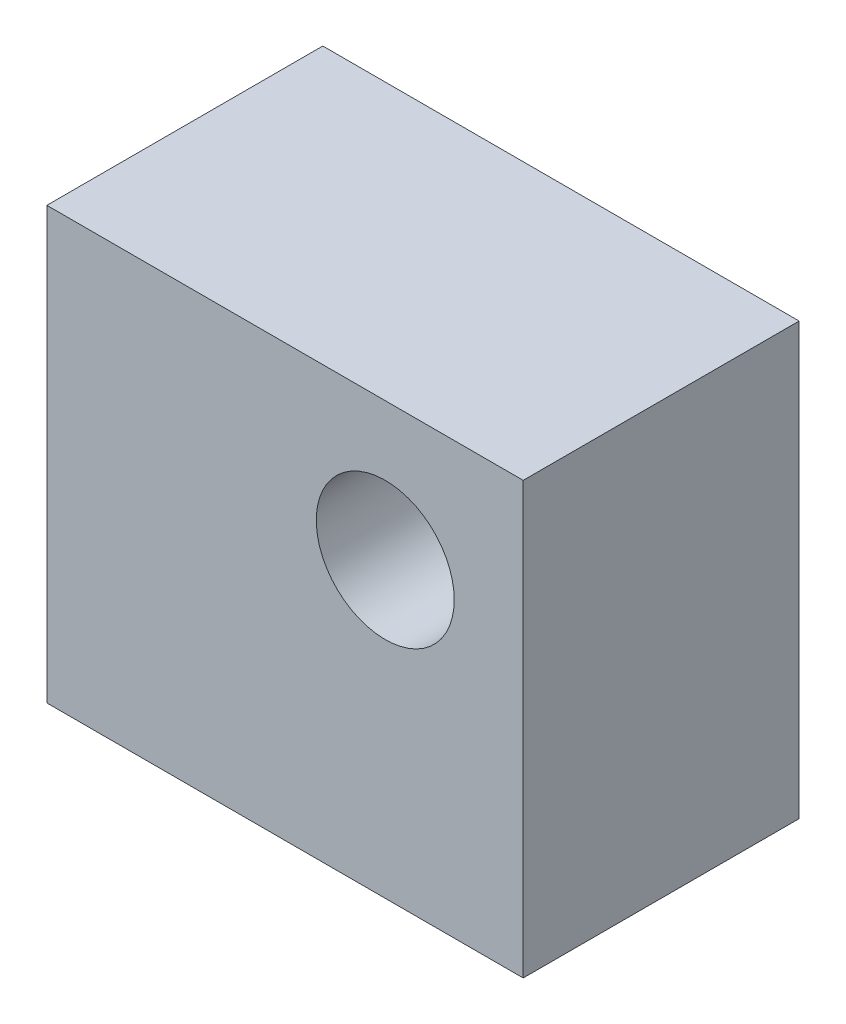
SolidWorks part; units mm, degrees
material "1060 Alloy"
ref_plane "Front" through (0, 0, 0) normal (0, 0, 1) x (1, 0, 0)
ref_plane "Top" through (0, 0, 0) normal (0, 1, 0) x (1, 0, 0)
ref_plane "Right" through (0, 0, 0) normal (1, 0, 0) x (0, 0, -1)
sketch "Sketch3" plane through (0, 0, 0) normal (0, 0, 1) x (1, 0, 0)
  line L0 (-0.127, -6.35) -> (30.1755, -6.35)
  line L1 (0, 0) -> (21.9242, 0)
  line L2 (0, 0) -> (0, -19.8376)
  line L3 (0, -19.8376) -> (21.9242, -19.8376)
  line L4 (21.9242, 0) -> (21.9242, -19.8376)
  line L5 (15.5742, -19.8376) -> (15.5742, 0) construction
  line L6 (15.5742, -6.35) -> (8.0621, -19.3614) construction
  line L15 (12.5496, -11.5887) -> (15.5742, -13.335) construction
  circle A0 centre (15.5742, -6.35) radius 6.0492 construction
  point P9 (0, 0)
  point P14 (0, -6.35)
  point P17 (9.525, -6.35)
  point P18 (31.1484, -6.35)
  point P19 (31.1484, 0)
  point P20 (7.7871, -19.8376)
  point P21 (0, 0)
  point P22 (0, 0)
  point P23 (15.5742, -19.8376)
  point P24 (15.5742, -19.8376)
  dimension "D2" = 6.35
  dimension "D6" = 3.4925
  dimension "D3" = 60
  dimension "D1" = 9.525
  dimension "D4" = 9.525
  dimension "D5" = 6.35
extrude "Boss-Extrude1" add sketch "Sketch3" along normal mid plane 12.7
sketch "Sketch4" plane through (0, 0, 0) normal (-1, 0, 0) x (0, 0, 1)
  circle A0 centre (0, -6.35) radius 3.175
  dimension "D1" = 6.35
extrude "Cut-Extrude1" cut sketch "Sketch4" against normal blind 9.525
ref_plane "Plane1" through (7.7871, -19.8376, 0) normal (-0.5, -0.866, 0) x (-0.866, 0.5, 0)
ref_plane "Mirror Plane" through (15.5742, 0, 0) normal (-1, 0, 0) x (0, 0, 1)
sketch "Sketch5" plane through (7.7871, -19.8376, 0) normal (-0.5, -0.866, 0) x (-0.866, 0.5, 0)
  circle A0 centre (0, 0) radius 3.175
  dimension "D1" = 6.35
extrude "Cut-Extrude5" cut sketch "Sketch5" against normal blind 9.525 and the other way up to next
sketch "Sketch6" plane through (0, 0, 6.35) normal (0, 0, -1) x (-1, 0, 0)
  circle A0 centre (-15.5742, -6.35) radius 3.175
  dimension "D1" = 6.35
extrude "Cut-Extrude6" cut sketch "Sketch6" along normal blind 9.525
equation "\"truss_member_od\" = .25in"
equation "\"truss_member_id\" = 0in"
equation "\"truss_member_L1\" = 2.75in"
equation "\"connector_hole_depth\" = .375in"
equation "\"D1@Boss-Extrude1\"=\"truss_member_od\"*2"
equation "\"D6@Sketch3\"=\"truss_member_od\"/2*1.1"
equation "\"D1@Sketch4\"=\"truss_member_od\""
equation "\"D1@Cut-Extrude1\"=\"connector_hole_depth\""
equation "\"D1@Sketch3\"=\"connector_hole_depth\""
equation "\"D4@Sketch3\"=\"connector_hole_depth\""
equation "\"D1@Sketch5\"=\"truss_member_od\""
equation "\"D1@Cut-Extrude5\"=\"connector_hole_depth\""
equation "\"D1@Cut-Extrude6\"=\"connector_hole_depth\""
equation "\"D1@Sketch6\"=\"truss_member_od\""
equation "\"D5@Sketch3\"=\"truss_member_od\""
